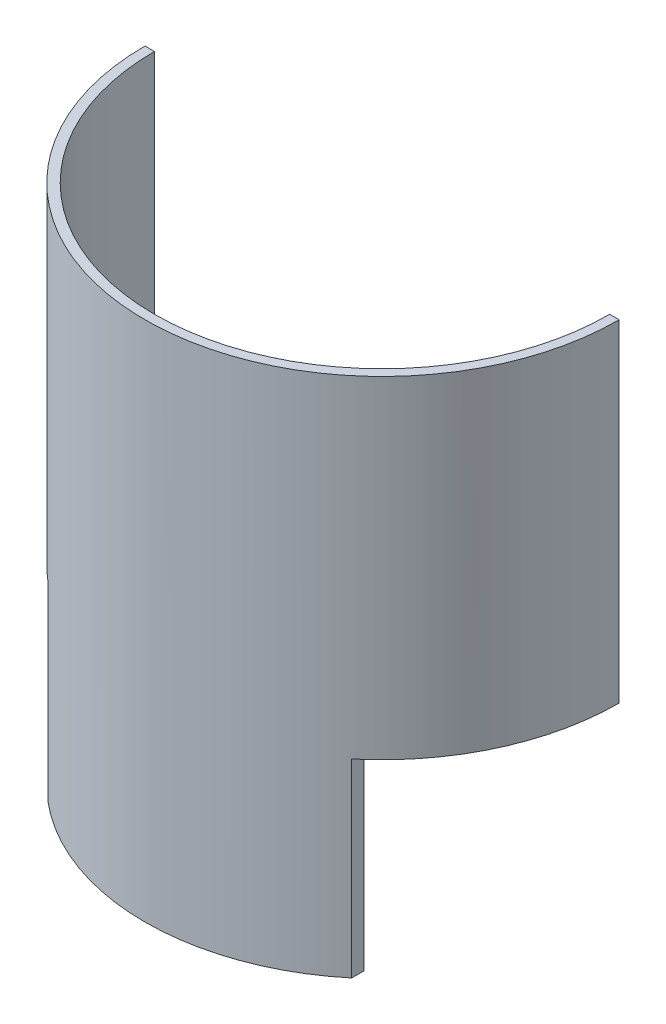
SolidWorks part; units mm, degrees
material "Rubber"
ref_plane "Front Plane" through (0, 0, 0) normal (0, 0, 1) x (1, 0, 0)
ref_plane "Top Plane" through (0, 0, 0) normal (0, 1, 0) x (1, 0, 0)
ref_plane "Right Plane" through (0, 0, 0) normal (1, 0, 0) x (0, 0, -1)
sketch "Sketch1" plane through (0, 0, 0) normal (0, 1, 0) x (1, 0, 0)
  line L0 (-12.5, 0) -> (-12, 0)
  line L1 (12, 0) -> (12.5, 0)
  line L2 (-8, -8.9443) -> (-8, -9.6047)
  line L3 (8, -8.9443) -> (8, -9.6047)
  arc A0 (-12.5, 0) -> (12.5, 0) centre (0, 0) ccw
  arc A1 (-12, 0) -> (12, 0) centre (0, 0) ccw
  dimension "D1" = 12.5
  dimension "D2" = 12
  dimension "D3" = 16
extrude "Boss-Extrude1" add sketch "Sketch1" along normal blind 10 contours A1 L2 A0 L3 region at (-7.8361, 0, 9.2745)
extrude "Boss-Extrude2" add sketch "Sketch1<3>" along normal blind 17.5 from offset 10 contours A1 L0 A0 L2 | A1 L2 A0 L3 | A1 L3 A0 L1 region at (-12.25, 0, 0.1061) region at (-7.8361, 0, 9.2745) region at (8.1061, 0, 9.2745)
sketch "Sketch1<3>" plane through (0, 0, 0) normal (0, 1, 0) x (1, 0, 0) same geometry as "Sketch1"
sketch "Sketch2" plane through (0, 0, 0) normal (0, -1, 0) x (1, 0, 0)
  line L0 (8, 8.9443) -> (8, 9.6047) construction
  line L1 (-8, 8.9443) -> (-8, 9.6047) construction
  line L2 (8, 8.9443) -> (8, 9.6047)
  line L3 (-8, 8.9443) -> (-8, 9.6047)
  arc A0 (8, 8.9443) -> (-8, 8.9443) centre (0, 0) ccw construction
  arc A1 (8, 9.6047) -> (-8, 9.6047) centre (0, 0) ccw construction
  arc A2 (8, 8.9443) -> (-8, 8.9443) centre (0, 0) ccw
  arc A3 (8, 9.6047) -> (-8, 9.6047) centre (0, 0) ccw
extrude "Cut-Extrude1" cut sketch "Sketch2" against normal blind 10
extrude "Boss-Extrude3" add sketch "Sketch2<2>" against normal up to surface (10 mm away) contours L3 A3 L2 A2 up to face at (0, 10, 6.125)
sketch "Sketch2<2>" plane through (0, 0, 0) normal (0, -1, 0) x (1, 0, 0) same geometry as "Sketch2"
